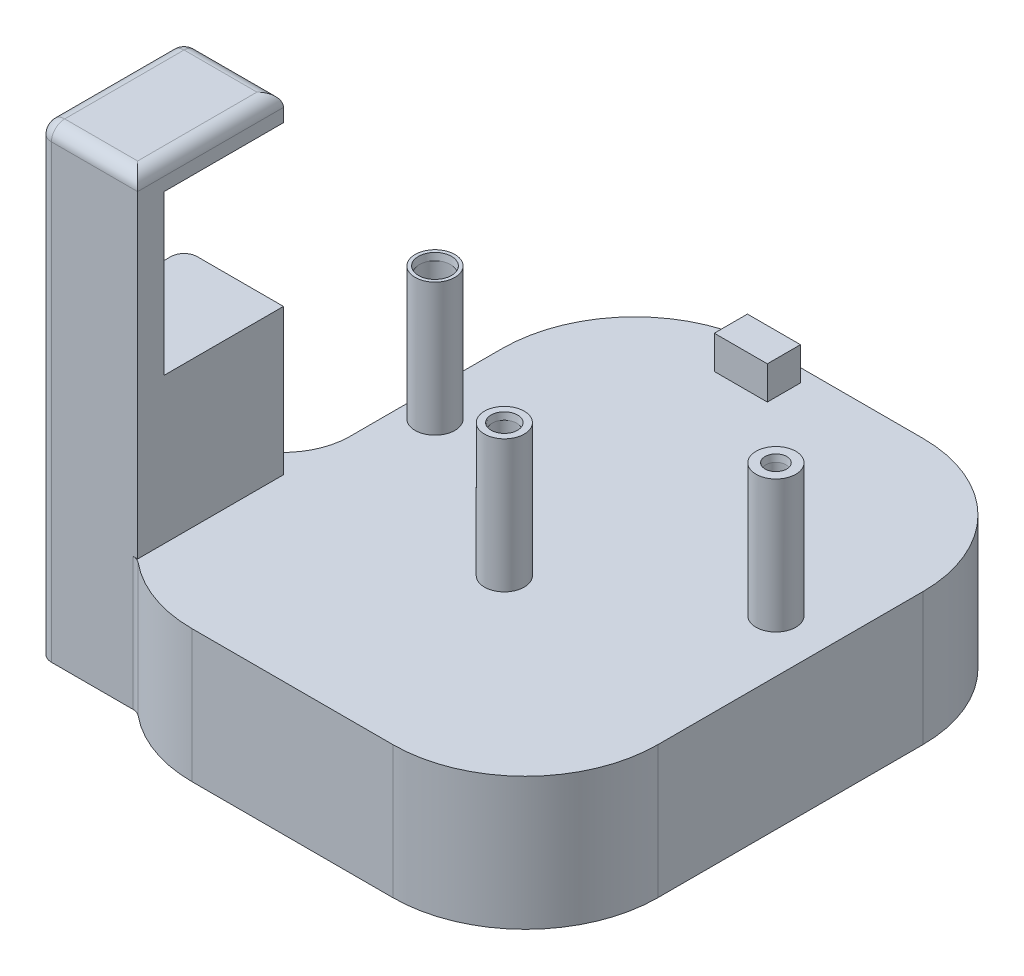
SolidWorks part; units mm, degrees
ref_plane "Front Plane" through (0, 0, 0) normal (0, 0, 1) x (1, 0, 0)
ref_plane "Top Plane" through (0, 0, 0) normal (0, 1, 0) x (1, 0, 0)
ref_plane "Right Plane" through (0, 0, 0) normal (1, 0, 0) x (0, 0, -1)
sketch "Sketch5" plane through (0, 0, 0) normal (0, 1, 0) x (1, 0, 0)
  line L1 (31.75, 40) -> (-31.75, 40)
  line L2 (31.75, 40) -> (31.75, -40)
  line L3 (31.75, -40) -> (-31.75, -40)
  line L4 (-31.75, 40) -> (-31.75, -40)
  line L5 (31.75, 40) -> (-31.75, -40) construction
  line L6 (31.75, -40) -> (-31.75, 40) construction
  point P0 (0, 0)
  dimension "D1" = 80
  dimension "D2" = 63.5
extrude "Boss-Extrude4" add sketch "Sketch5" along normal blind 20
sketch "Sketch6" plane through (0, 20, 0) normal (0, 1, 0) x (1, 0, 0)
  line L0 (31.75, 40) -> (-31.75, 40) construction
  line L1 (-4.75, 38) -> (-12.75, 38)
  line L2 (-4.75, 38) -> (-4.75, 33)
  line L3 (-4.75, 33) -> (-12.75, 33)
  line L4 (-12.75, 38) -> (-12.75, 33)
  line L5 (-4.75, 38) -> (-12.75, 33) construction
  line L6 (-4.75, 33) -> (-12.75, 38) construction
  line L9 (0, 0) -> (0, 40) construction
  line L10 (-31.75, 40) -> (-31.75, -40) construction
  point P0 (-8.75, 35.5)
  dimension "D1" = 8
  dimension "D2" = 5
  dimension "D3" = 2
  dimension "D4" = 19
extrude "Boss-Extrude5" add sketch "Sketch6" along normal blind 5 contours L3 L4 L1 L2
sketch "Sketch9" plane through (0, 0, 0) normal (0, 1, 0) x (1, 0, 0)
  line L0 (-31.75, 40) -> (-31.75, -40) construction
  line L5 (-31.75, -35) -> (-46.75, -35)
  line L6 (-31.75, -35) -> (-31.75, -13)
  line L7 (-31.75, -13) -> (-46.75, -13)
  line L8 (-46.75, -35) -> (-46.75, -13)
  line L9 (-31.75, -40) -> (31.75, -40) construction
  point P13 (-39.25, -13)
  dimension "D4" = 5
  dimension "D5" = 22
  dimension "D6" = 7.5
sketch "Sketch13" plane through (0, 20, 0) normal (0, 1, 0) x (1, 0, 0)
  line L0 (-31.75, 40) -> (-31.75, -40) construction
  line L2 (-31.75, -40) -> (31.75, -40) construction
  circle A0 centre (-27.6098, 5.72) radius 3
  circle A1 centre (23.8252, 5.72) radius 3
  circle A2 centre (-1.905, -9.52) radius 3
  dimension "D1" = 4.1402
  dimension "D3" = 6
  dimension "D4" = 51.435
  dimension "D6" = 6
  dimension "D7" = 6
  dimension "D2" = 45.72
  dimension "D5" = 45.72
  dimension "D8" = 25.7048
  dimension "D9" = 15.24
extrude "Boss-Extrude8" add sketch "Sketch13" along normal blind 20
extrude "Boss-Extrude10" add sketch "Sketch9" along normal blind 70 contours L8 L7 L6 L5
sketch "Sketch14" plane through (0, 0, 13) normal (0, 0, -1) x (-1, 0, 0)
  line L0 (31.75, 70) -> (31.75, 20) construction
  line L1 (31.75, 42) -> (46.75, 42)
  line L2 (31.75, 42) -> (31.75, 66)
  line L3 (31.75, 66) -> (46.75, 66)
  line L4 (46.75, 42) -> (46.75, 66)
  line L5 (46.75, 70) -> (46.75, 0) construction
  line L7 (31.75, 0) -> (46.75, 0) construction
  dimension "D1" = 42
  dimension "D2" = 24
extrude "Cut-Extrude1" cut sketch "Sketch14" against normal blind 18 contours L3 L4 L1 L2
fillet "Fillet1" radius 20 4 edges at (-31.75, 10, -40) (31.75, 10, -40) (-31.75, 10, 40) (31.75, 10, 40)
fillet "Fillet2" radius 10 1 edges at (-31.75, 10, 13)
fillet "Fillet3" radius 2 3 edges at (-31.75, 10, 35) (-46.75, 35, 35) (-46.75, 21, 13)
fillet "Fillet4" radius 2 1 edges at (-46.75, 68, 13)
fillet "Fillet6" radius 2 6 edges at (-31.75, 70, 24) (-38.25, 70, 35) (-46.1642, 70, 34.4142) (-46.75, 70, 24) (-46.1642, 70, 13.5858) (-38.25, 70, 13)
sketch "Sketch15" plane through (0, 40, 0) normal (0, 1, 0) x (1, 0, 0)
  circle A0 centre (23.8252, 5.72) radius 1.6383
  circle A1 centre (23.8252, 5.72) radius 3 construction
  circle A2 centre (-1.905, -9.52) radius 2
  circle A5 centre (-27.6098, 5.72) radius 2.5
  dimension "D1" = 3.2766
  dimension "D3" = 4
  dimension "D4" = 5
  dimension "D2" = 0
extrude "Cut-Extrude2" cut sketch "Sketch15" against normal blind 1 draft 8
sketch "Sketch16" plane through (0, 39, 0) normal (0, 1, 0) x (1, 0, 0)
  circle A0 centre (23.8252, 5.72) radius 1.4986
  circle A1 centre (23.8252, 5.72) radius 3 construction
  circle A2 centre (-1.905, -9.52) radius 2
  circle A3 centre (-27.6098, 5.72) radius 2.5
  dimension "D1" = 2.9972
  dimension "D3" = 4
  dimension "D4" = 5
  dimension "D2" = 0
extrude "Cut-Extrude3" cut sketch "Sketch16" against normal blind 7
